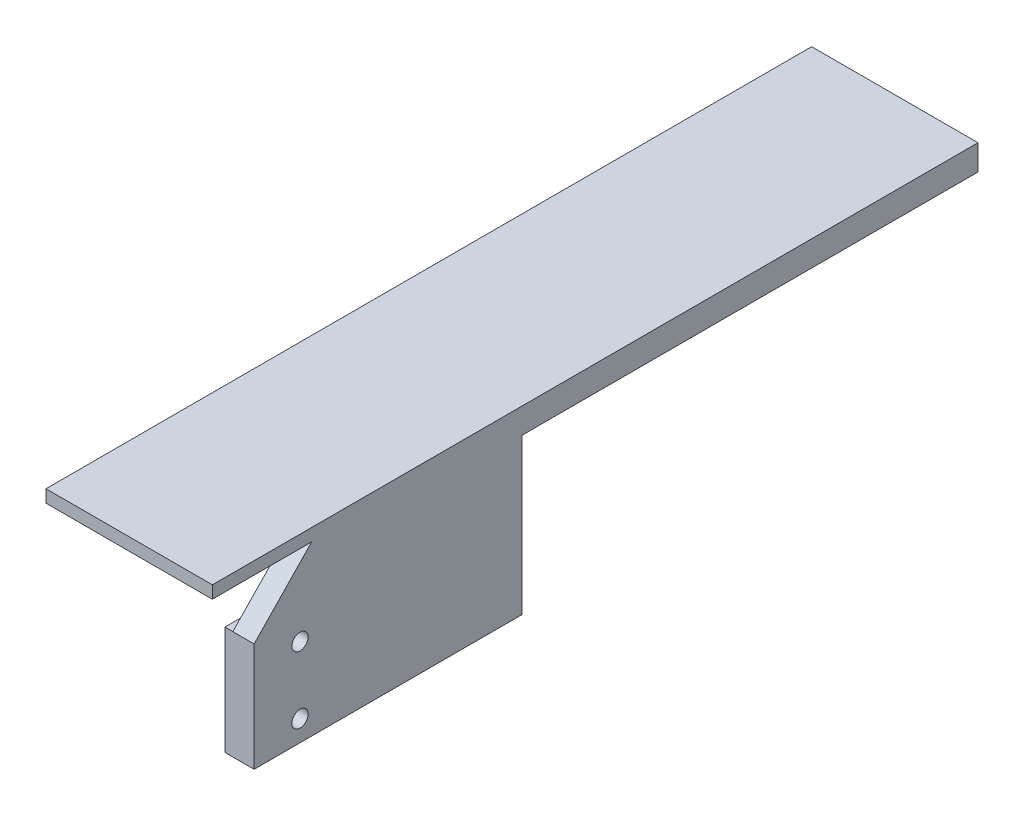
SolidWorks part; units mm, degrees
ref_plane "Front Plane" through (0, 0, 0) normal (0, 0, 1) x (1, 0, 0)
ref_plane "Top Plane" through (0, 0, 0) normal (0, 1, 0) x (1, 0, 0)
ref_plane "Right Plane" through (0, 0, 0) normal (1, 0, 0) x (0, 0, -1)
ref_plane "PY -20.700" through (0, -20.7, 0) normal (0, 1, 0) x (1, 0, 0)
sketch "leg and pad sketch" plane through (0, -20.7, 0) normal (0, 1, 0) x (1, 0, 0)
  line L0 (-0.5513, 30.3327) -> (-0.3673, 30.8194)
  line L1 (-0.3673, 30.8194) -> (-0.028, 31.2139)
  line L2 (-0.028, 31.2139) -> (0.4256, 31.4688)
  line L3 (0.4256, 31.4688) -> (0.939, 31.5534)
  line L4 (0.939, 31.5534) -> (1.4504, 31.4576)
  line L5 (1.4504, 31.4576) -> (1.8983, 31.1928)
  line L6 (1.8983, 31.1928) -> (2.2288, 30.7909)
  line L7 (2.2288, 30.7909) -> (2.4021, 30.3003)
  line L8 (2.4021, 30.3003) -> (2.3973, 29.78)
  line L9 (2.3973, 29.78) -> (2.2152, 29.2926)
  line L10 (2.2152, 29.2926) -> (1.8775, 28.8968)
  line L11 (1.8775, 28.8968) -> (1.4248, 28.6402)
  line L12 (1.4248, 28.6402) -> (0.9118, 28.5536)
  line L13 (0.9118, 28.5536) -> (0.4, 28.6475)
  line L14 (0.4, 28.6475) -> (0.4, -9.98)
  line L15 (0.4, -9.98) -> (1.92, -11.5)
  line L16 (1.92, -11.5) -> (1.92, -31.37)
  line L17 (1.92, -31.37) -> (8.92, -31.37)
  line L18 (8.92, -31.37) -> (8.92, 32.7926)
  line L19 (8.92, 32.7926) -> (-27.2048, 54.5947)
  line L20 (-27.2048, 54.5947) -> (-30.8218, 48.6015)
  line L21 (-30.8218, 48.6015) -> (-0.5513, 30.3327)
extrude "leg and pad" add sketch "leg and pad sketch" along normal mid plane 26
ref_plane "PX 1.350" through (1.35, 0, 0) normal (1, 0, 0) x (0, 0, -1)
sketch "screw head relief sketch" plane through (1.35, 0, 0) normal (1, 0, 0) x (0, 0, -1)
  line L0 (23.4, -12.7) -> (23.4, -6.7)
  line L1 (23.4, -6.7) -> (9.4, -6.7)
  line L2 (9.4, -6.7) -> (9.4, -12.7)
  line L3 (9.4, -12.7) -> (23.4, -12.7)
extrude "screw head relief" cut sketch "screw head relief sketch" against normal mid plane 4.7
sketch "insert flange relief sketch" plane through (0, -20.7, 0) normal (0, 1, 0) x (1, 0, 0)
  line L0 (-18.3249, 39.8914) -> (-17.0331, 42.0318)
  line L1 (-17.0331, 42.0318) -> (-9.7557, 37.6398)
  line L2 (-9.7557, 37.6398) -> (-11.0475, 35.4994)
  line L3 (-11.0475, 35.4994) -> (-18.3249, 39.8914)
revolve "insert flange relief" cut sketch "insert flange relief sketch" angle 360 about L0
sketch "M6 slot end 1 sketch" plane through (0, -20.7, 0) normal (0, 1, 0) x (1, 0, 0)
  line L0 (-20.8933, 41.4415) -> (-16.243, 49.147)
  line L1 (-16.243, 49.147) -> (-13.2464, 47.3385)
  line L2 (-13.2464, 47.3385) -> (-17.8968, 39.633)
  line L3 (-17.8968, 39.633) -> (-20.8933, 41.4415)
revolve "M6 slot end 1" cut sketch "M6 slot end 1 sketch" angle 360 about L0
sketch "M6 slot end 2 sketch" plane through (0, -20.7, 0) normal (0, 1, 0) x (1, 0, 0)
  line L0 (-15.7564, 38.3413) -> (-11.106, 46.0467)
  line L1 (-11.106, 46.0467) -> (-8.1094, 44.2382)
  line L2 (-8.1094, 44.2382) -> (-12.7598, 36.5328)
  line L3 (-12.7598, 36.5328) -> (-15.7564, 38.3413)
revolve "M6 slot end 2" cut sketch "M6 slot end 2 sketch" angle 360 about L0
sketch "M6 slot middle sketch" plane through (0, -20.7, 0) normal (0, 1, 0) x (1, 0, 0)
  line L0 (-15.7564, 38.3413) -> (-20.8933, 41.4415)
  line L1 (-20.8933, 41.4415) -> (-16.243, 49.147)
  line L2 (-16.243, 49.147) -> (-11.106, 46.0467)
  line L3 (-11.106, 46.0467) -> (-15.7564, 38.3413)
extrude "M6 slot middle" cut sketch "M6 slot middle sketch" against normal mid plane 7
ref_plane "PX 5.420" through (5.42, 0, 0) normal (1, 0, 0) x (0, 0, -1)
sketch "screw holes sketch" plane through (5.42, 0, 0) normal (1, 0, 0) x (0, 0, -1)
  circle A0 centre (-20.375, -28.7) radius 1.95
  circle A1 centre (-20.375, -12.7) radius 1.95
extrude "screw holes" cut sketch "screw holes sketch" against normal mid plane 9
ref_plane "PY -2.100" through (0, -2.1, 0) normal (0, 1, 0) x (1, 0, 0)
sketch "foot leg sketch" plane through (0, -2.1, 0) normal (0, 1, 0) x (1, 0, 0)
  line L0 (2.3, 30.0135) -> (2.3, -9.98)
  line L1 (2.3, -9.98) -> (8.92, -9.98)
  line L2 (8.92, -9.98) -> (8.92, 32.7926)
  line L3 (8.92, 32.7926) -> (-27.2048, 54.5947)
  line L4 (-27.2048, 54.5947) -> (-30.2017, 49.6289)
  line L5 (-30.2017, 49.6289) -> (2.3, 30.0135)
extrude "foot leg" add sketch "foot leg sketch" along normal mid plane 12.2
ref_plane "PY 6.535" through (0, 6.535, 0) normal (0, 1, 0) x (1, 0, 0)
sketch "sole under the housing sketch" plane through (0, 6.535, 0) normal (0, 1, 0) x (1, 0, 0)
  line L0 (-30.9218, 142) -> (8.92, 142)
  line L1 (8.92, 142) -> (8.92, -13.03)
  line L2 (8.92, -13.03) -> (-30.9218, -13.03)
  line L3 (-30.9218, -13.03) -> (-30.9218, 142)
extrude "sole under the housing" add sketch "sole under the housing sketch" along normal mid plane 6.07
ref_plane "PY 8.070" through (0, 8.07, 0) normal (0, 1, 0) x (1, 0, 0)
sketch "sole under the block sketch" plane through (0, 8.07, 0) normal (0, 1, 0) x (1, 0, 0)
  line L0 (-30.9218, -12.53) -> (8.92, -12.53)
  line L1 (8.92, -12.53) -> (8.92, -41.37)
  line L2 (8.92, -41.37) -> (-30.9218, -41.37)
  line L3 (-30.9218, -41.37) -> (-30.9218, -12.53)
extrude "sole under the block" add sketch "sole under the block sketch" along normal mid plane 3
ref_plane "PX 6.370" through (6.37, 0, 0) normal (1, 0, 0) x (0, 0, -1)
sketch "seat gusset sketch" plane through (6.37, 0, 0) normal (1, 0, 0) x (0, 0, -1)
  line L0 (-9.48, -8.2) -> (-31.37, -8.2)
  line L1 (-31.37, -8.2) -> (-31.37, -7.7)
  line L2 (-31.37, -7.7) -> (-17.1, 7.07)
  line L3 (-17.1, 7.07) -> (-9.48, 7.07)
  line L4 (-9.48, 7.07) -> (-9.48, -8.2)
extrude "seat gusset" add sketch "seat gusset sketch" along normal mid plane 5.1
ref_plane "PX -19.922" through (-19.9218, 0, 0) normal (1, 0, 0) x (0, 0, -1)
sketch "tail rib sketch" plane through (-19.9218, 0, 0) normal (1, 0, 0) x (0, 0, -1)
  line L0 (53.1, 4) -> (53.1, -12.5)
  line L1 (53.1, -12.5) -> (57.1, -12.5)
  line L2 (57.1, -12.5) -> (140, 3.5)
  line L3 (140, 3.5) -> (140, 4)
  line L4 (140, 4) -> (53.1, 4)
extrude "tail rib" add sketch "tail rib sketch" along normal mid plane 6
sketch "screw head relief to the end sketch" plane through (1.35, 0, 0) normal (1, 0, 0) x (0, 0, -1)
  line L0 (23.4, -12.7) -> (23.4, 3.3)
  line L1 (23.4, 3.3) -> (9.4, 3.3)
  line L2 (9.4, 3.3) -> (9.4, -12.7)
  line L3 (9.4, -12.7) -> (23.4, -12.7)
extrude "screw head relief to the end" cut sketch "screw head relief to the end sketch" against normal mid plane 4.7
equation "\"diffL\" = 608.8mm"
equation "\"diffW\" = 329.4mm"
equation "\"diffT\" = 2.9mm"
equation "\"chanSlotW\" = 12.9mm"
equation "\"chanSlotDepth\" = 11.13mm"
equation "\"chanFloor\" = 1.57mm"
equation "\"chanLeg\" = 12.7mm"
equation "\"lightL\" = 604.8mm"
equation "\"lightW\" = 330.2mm"
equation "\"lightH\" = 92mm"
equation "\"lightSideFlat\" = 30mm"
equation "\"lightSlopeLen\" = 38.9mm"
equation "\"lightWingDepth\" = 50.1mm"
equation "\"lightWingFlat\" = 90.2mm"
equation "\"lightChanW\" = 99.6mm"
equation "\"lightChanStand\" = 44.1mm"
equation "\"insFlangeD\" = 12.3mm"
equation "\"insFromEnd\" = 20.7mm"
equation "\"insUpSlope\" = 20.8mm"
equation "\"gaugeH\" = 10mm"
equation "\"gaugeStepLen\" = 14mm"
equation "\"gaugeStepW0\" = 13.1mm"
equation "\"gaugeStepDW\" = 0.2mm"
equation "\"gaugeSteps\" = 5mm"
equation "\"gaugeHandleLen\" = 30mm"
equation "\"gaugeHandleW\" = 24mm"
equation "\"gaugeSlot0\" = 3mm"
equation "\"gaugeSlotD\" = 0.1mm"
equation "\"gaugeSlotDepth\" = 8mm"
equation "\"gap\" = 25.4mm"
equation "\"edgeL\" = 1mm"
equation "\"edgeW\" = 0.75mm"
equation "\"proud\" = 1.5mm"
equation "\"seatClr\" = 0.15mm"
equation "\"tongueClrZ\" = 0.1mm"
equation "\"tongueClrX\" = 0.25mm"
equation "\"tongueLen\" = 30mm"
equation "\"armSide\" = 45mm"
equation "\"armEnd\" = 20mm"
equation "\"cornerCham\" = 3mm"
equation "\"brkW\" = 26mm"
equation "\"brkT\" = 7mm"
equation "\"brkSeatClr\" = 0.3mm"
equation "\"brkScrewSpan\" = 16mm"
equation "\"pilotD\" = 2.7mm"
equation "\"pilotDepth\" = 10mm"
equation "\"screwClrD\" = 3.9mm"
equation "\"jogBelow\" = 4mm"
equation "\"padT\" = 7mm"
equation "\"padLen\" = 36mm"
equation "\"m6Clr\" = 7mm"
equation "\"m6Slot\" = 6mm"
equation "\"flangeRelD\" = 17mm"
equation "\"flangeRelDepth\" = 1.5mm"
equation "\"relLen\" = 5mm"
equation "\"relDepth\" = 3.3mm"
equation "\"knockN\" = 100mm"
equation "\"petgcfE\" = 3000mm"
equation "\"mockExtent\" = 110mm"
equation "\"relZnear\" = 9.4mm"
equation "\"relZfar\" = 23.4mm"
equation "\"headD\" = 8mm"
equation "\"headH\" = 2.5mm"
equation "\"headFromEnd\" = 6.8mm"
equation "\"headBack\" = 16.4mm"
equation "\"sideClr\" = 0.4mm"
equation "\"cornerRelR\" = 1.5mm"
equation "\"cornerRelBack\" = 0.6mm"
equation "\"endHeadH\" = 2.8mm"
equation "\"footClr\" = 1.2mm"
equation "\"footEndClr\" = 3.5mm"
equation "\"footLift\" = 3.5mm"
equation "\"footBlockClr\" = 0.5mm"
equation "\"footBack\" = 30mm"
equation "\"footFwd\" = 25mm"
equation "\"footRibH\" = 16mm"
equation "\"footRibT\" = 6mm"
